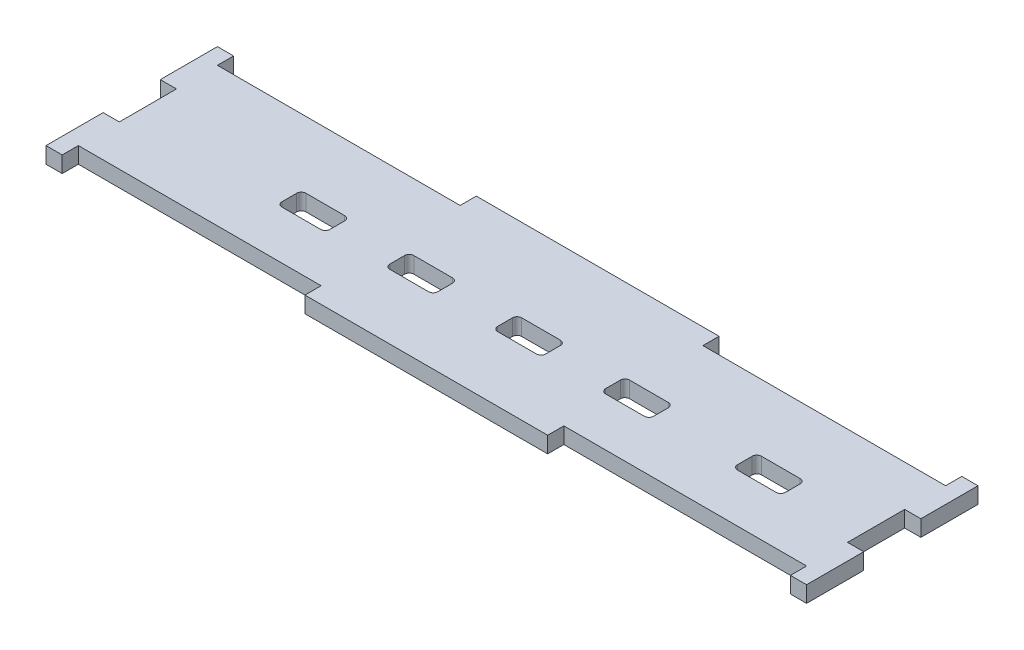
SolidWorks part; units mm, degrees
ref_plane "Front Plane" through (0, 0, 0) normal (0, 0, 1) x (1, 0, 0)
ref_plane "Top Plane" through (0, 0, 0) normal (0, 1, 0) x (1, 0, 0)
ref_plane "Right Plane" through (0, 0, 0) normal (1, 0, 0) x (0, 0, -1)
sketch "Sketch1" plane through (0, 0, 0) normal (0, 1, 0) x (1, 0, 0)
  line L6 (4, 2.8333) -> (4, 12.3667)
  line L8 (-117.5, 12.3667) -> (-117.5, 2.8333)
  line L11 (6.7, -6.7) -> (4, -6.7)
  line L13 (-117.5, -6.7) -> (-120.2, -6.7)
  line L14 (-120.2, 21.9) -> (-120.2, 12.3667)
  line L17 (6.7, -6.7) -> (6.7, 2.8333)
  line L21 (-111.5, -4) -> (-117.5, -4) construction
  line L22 (4, -4) -> (-111.5, -4) construction
  line L23 (-117.5, -4) -> (-77, -4)
  line L25 (-120.2, 21.9) -> (-120.2, -6.7) construction
  line L26 (-120.2, 2.8333) -> (-120.2, -6.7)
  line L28 (-36.5, -4) -> (4, -4)
  line L29 (-120.2, 2.8333) -> (-117.5, 2.8333)
  line L30 (-120.2, 12.3667) -> (-117.5, 12.3667)
  line L31 (-77, -4) -> (-77, -6.7)
  line L32 (-36.5, -4) -> (-36.5, -6.7)
  line L33 (-117.5, -4) -> (-117.5, -6.7)
  line L34 (-117.5, 19.2) -> (-117.5, 21.9)
  line L35 (-117.5, 19.2) -> (-117.5, -4) construction
  line L36 (-111.5, -6.7) -> (-120.2, -6.7) construction
  line L37 (6.7, -6.7) -> (-111.5, -6.7) construction
  line L39 (6.7, -6.7) -> (6.7, 21.9) construction
  line L40 (6.7, 12.3667) -> (6.7, 21.9)
  line L41 (6.7, 12.3667) -> (4, 12.3667)
  line L42 (6.7, 2.8333) -> (4, 2.8333)
  line L43 (4, -4) -> (4, -6.7)
  line L44 (4, 19.2) -> (4, 21.9)
  line L45 (4, -4) -> (4, 19.2) construction
  line L46 (-36.5, -6.7) -> (-77, -6.7)
  line L47 (4, 19.2) -> (-111.5, 19.2) construction
  line L48 (-111.5, 19.2) -> (-117.5, 19.2) construction
  line L49 (6.7, 21.9) -> (-111.5, 21.9) construction
  line L50 (-111.5, 21.9) -> (-120.2, 21.9) construction
  line L51 (-120.2, 21.9) -> (-117.5, 21.9)
  line L52 (6.7, 21.9) -> (4, 21.9)
  line L54 (-36.5, 19.2) -> (4, 19.2)
  line L55 (-36.5, 19.2) -> (-36.5, 21.9)
  line L56 (-36.5, 21.9) -> (-77, 21.9)
  line L57 (-77, 19.2) -> (-77, 21.9)
  line L58 (-117.5, 19.2) -> (-77, 19.2)
  line L59 (-91.6279, 8.1) -> (-85.1721, 8.1)
  line L60 (-92.4, 7.3279) -> (-92.4, 4.8721)
  line L61 (-91.6279, 4.1) -> (-85.1721, 4.1)
  line L62 (-84.4, 7.3279) -> (-84.4, 4.8721)
  line L63 (-92.4, 8.1) -> (-84.4, 4.1) construction
  line L64 (-92.4, 4.1) -> (-84.4, 8.1) construction
  line L65 (-73.6279, 8.1) -> (-67.1721, 8.1)
  line L66 (-74.4, 7.3279) -> (-74.4, 4.8721)
  line L67 (-73.6279, 4.1) -> (-67.1721, 4.1)
  line L68 (-66.4, 7.3279) -> (-66.4, 4.8721)
  line L69 (-74.4, 8.1) -> (-66.4, 4.1) construction
  line L70 (-74.4, 4.1) -> (-66.4, 8.1) construction
  line L71 (-55.6279, 8.1) -> (-49.1721, 8.1)
  line L72 (-56.4, 7.3279) -> (-56.4, 4.8721)
  line L73 (-55.6279, 4.1) -> (-49.1721, 4.1)
  line L74 (-48.4, 7.3279) -> (-48.4, 4.8721)
  line L75 (-56.4, 8.1) -> (-48.4, 4.1) construction
  line L76 (-56.4, 4.1) -> (-48.4, 8.1) construction
  line L77 (-37.6279, 8.1) -> (-31.1721, 8.1)
  line L78 (-38.4, 7.3279) -> (-38.4, 4.8721)
  line L79 (-37.6279, 4.1) -> (-31.1721, 4.1)
  line L80 (-30.4, 7.3279) -> (-30.4, 4.8721)
  line L81 (-38.4, 8.1) -> (-30.4, 4.1) construction
  line L82 (-38.4, 4.1) -> (-30.4, 8.1) construction
  line L83 (-15.6279, 8.1) -> (-9.1721, 8.1)
  line L84 (-16.4, 7.3279) -> (-16.4, 4.8721)
  line L85 (-15.6279, 4.1) -> (-9.1721, 4.1)
  line L86 (-8.4, 7.3279) -> (-8.4, 4.8721)
  line L87 (-16.4, 8.1) -> (-8.4, 4.1) construction
  line L88 (-16.4, 4.1) -> (-8.4, 8.1) construction
  arc A3 (-8.4, 4.8721) -> (-9.1721, 4.1) centre (-9.1721, 4.8721) cw
  arc A4 (-15.6279, 4.1) -> (-16.4, 4.8721) centre (-15.6279, 4.8721) cw
  arc A5 (-16.4, 7.3279) -> (-15.6279, 8.1) centre (-15.6279, 7.3279) cw
  arc A6 (-9.1721, 8.1) -> (-8.4, 7.3279) centre (-9.1721, 7.3279) cw
  arc A7 (-30.4, 7.3279) -> (-31.1721, 8.1) centre (-31.1721, 7.3279) ccw
  arc A8 (-37.6279, 8.1) -> (-38.4, 7.3279) centre (-37.6279, 7.3279) ccw
  arc A9 (-38.4, 4.8721) -> (-37.6279, 4.1) centre (-37.6279, 4.8721) ccw
  arc A10 (-31.1721, 4.1) -> (-30.4, 4.8721) centre (-31.1721, 4.8721) ccw
  arc A11 (-49.1721, 8.1) -> (-48.4, 7.3279) centre (-49.1721, 7.3279) cw
  arc A12 (-48.4, 4.8721) -> (-49.1721, 4.1) centre (-49.1721, 4.8721) cw
  arc A13 (-55.6279, 4.1) -> (-56.4, 4.8721) centre (-55.6279, 4.8721) cw
  arc A14 (-56.4, 7.3279) -> (-55.6279, 8.1) centre (-55.6279, 7.3279) cw
  arc A15 (-67.1721, 8.1) -> (-66.4, 7.3279) centre (-67.1721, 7.3279) cw
  arc A16 (-66.4, 4.8721) -> (-67.1721, 4.1) centre (-67.1721, 4.8721) cw
  arc A17 (-73.6279, 4.1) -> (-74.4, 4.8721) centre (-73.6279, 4.8721) cw
  arc A18 (-74.4, 7.3279) -> (-73.6279, 8.1) centre (-73.6279, 7.3279) cw
  arc A19 (-85.1721, 8.1) -> (-84.4, 7.3279) centre (-85.1721, 7.3279) cw
  arc A20 (-84.4, 4.8721) -> (-85.1721, 4.1) centre (-85.1721, 4.8721) cw
  arc A21 (-91.6279, 4.1) -> (-92.4, 4.8721) centre (-91.6279, 4.8721) cw
  arc A22 (-91.6279, 8.1) -> (-92.4, 7.3279) centre (-91.6279, 7.3279) ccw
  point P5 (-88.4, 6.1)
  point P7 (-12.4, 6.1)
  point P8 (-52.4, 6.1)
  point P9 (-34.4, 6.1)
  point P10 (-70.4, 6.1)
  point P11 (-88.4, 6.1)
  point P21 (-70.4, 6.1)
  point P52 (-52.4, 6.1)
  point P57 (-34.4, 6.1)
  point P62 (-12.4, 6.1)
  dimension "D9" = 8
  dimension "D13" = 4
  dimension "D19" = 0.7721
  dimension "D2" = 8
  dimension "D4" = 8
  dimension "D10" = 8
  dimension "D12" = 8
  dimension "D14" = 4
  dimension "D16" = 4
  dimension "D17" = 4
  dimension "D18" = 4
  dimension "D15" = 2.7
extrude "Boss-Extrude1" add sketch "Sketch1" along normal blind 2.7
